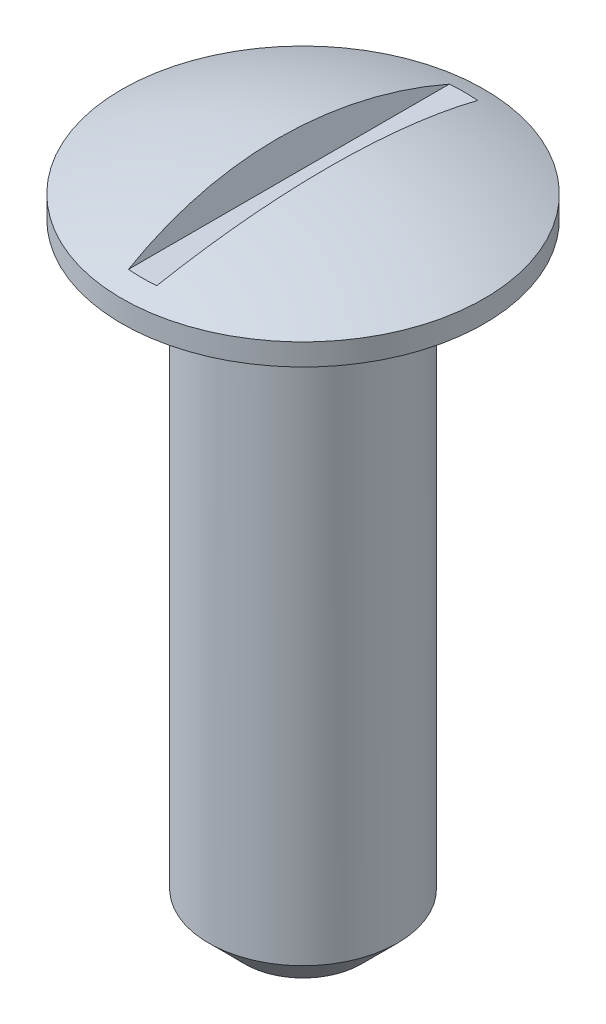
SolidWorks part; units mm, degrees
ref_plane "Front Plane" through (0, 0, 0) normal (0, 0, 1) x (1, 0, 0)
ref_plane "Top Plane" through (0, 0, 0) normal (0, 1, 0) x (1, 0, 0)
ref_plane "Right Plane" through (0, 0, 0) normal (1, 0, 0) x (0, 0, -1)
sketch "Sketch1" plane through (0, 0, 0) normal (0, 0, 1) x (1, 0, 0)
  line L0 (0, 1.2886) -> (0, -0.9236) construction
  line L1 (0, 0.8364) -> (-0.5, 0.8364)
  line L2 (-0.5, 0.8364) -> (-0.5, 0.7764)
  line L3 (-0.5, 0.7764) -> (-0.2604, 0.7764)
  line L4 (-0.2604, 0.7764) -> (-0.2604, -0.9236)
  line L5 (-0.2604, -0.9236) -> (0, -0.9236)
  line L6 (0, -0.9236) -> (0, 0.8364)
  dimension "D1" = 1.7
  dimension "D2" = 1
  dimension "D3" = 0.06
  dimension "D4" = 0.5
revolve "Revolve1" add sketch "Sketch1" angle 360 about L0
dome "Dome1" faces to dome 1 distance 0.1 reverse direction no elliptical dome no face at (-0.5, 0.8364, 0) parameters "D1"=0.1
sketch "Sketch2" plane through (0, 0, 0) normal (0, 0, 1) x (1, 0, 0)
  line L0 (0, 1.1267) -> (0, -1.0381) construction
  line L1 (-0.0694, 0.9346) -> (-0.039, 0.8581)
  line L2 (-0.039, 0.8581) -> (0.039, 0.8581)
  line L3 (0.0694, 0.9346) -> (0.039, 0.8581)
  arc A0 (0.5, 0.8364) -> (-0.5, 0.8364) centre (0, -0.3636) ccw construction
  point P9 (-0.1055, 0.9322)
  point P11 (0, 0.8581)
  point P12 (-0.039, 0.8581)
  point P13 (-0.0694, 0.9346)
extrude "Cut-Extrude2" cut sketch "Sketch2" against normal through all and the other way through all flip side to cut
chamfer "Chamfer1" distance 0.1 angle 45 1 edges at (-0.2604, -0.9236, 0)
